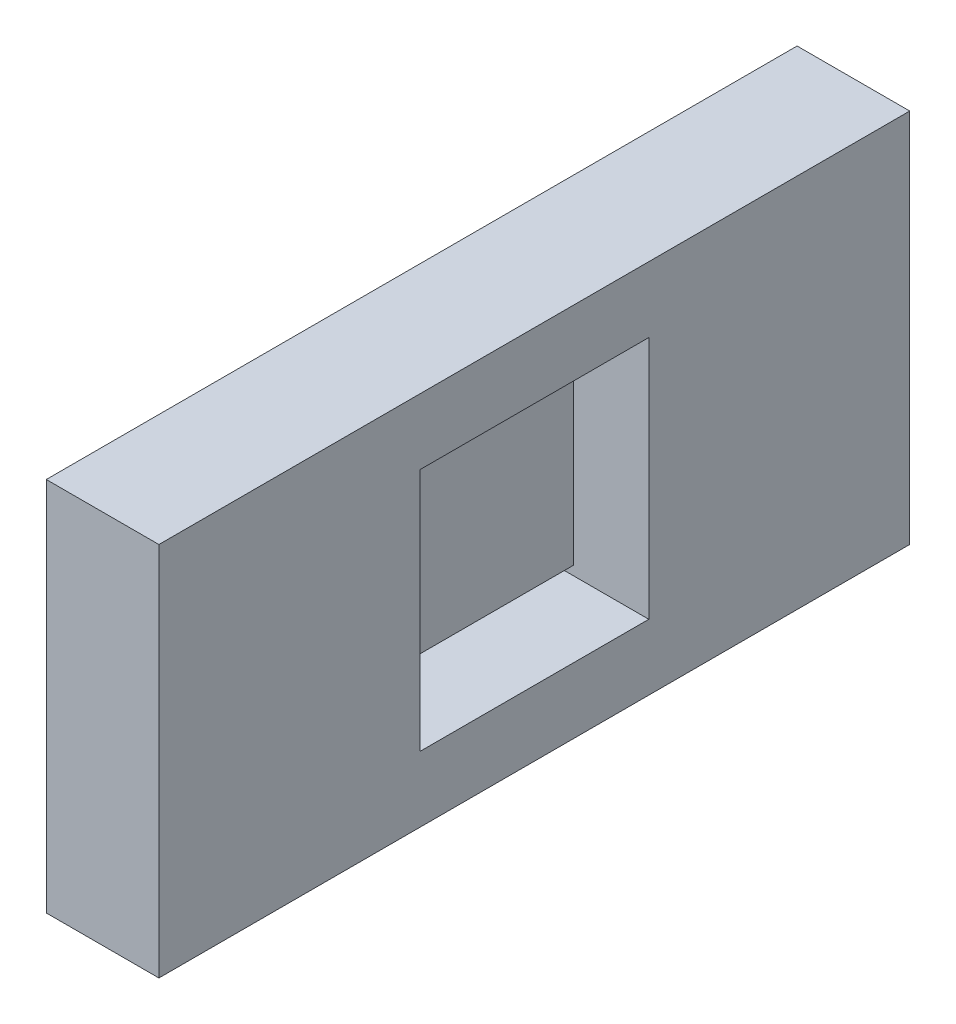
SolidWorks part; units mm, degrees
ref_plane "Front Plane" through (0, 0, 0) normal (0, 0, 1) x (1, 0, 0)
ref_plane "Top Plane" through (0, 0, 0) normal (0, 1, 0) x (1, 0, 0)
ref_plane "Right Plane" through (0, 0, 0) normal (1, 0, 0) x (0, 0, -1)
sketch "Sketch1" plane through (0, 0, 0) normal (1, 0, 0) x (0, 0, -1)
  line L1 (0, 0) -> (12.2, 0)
  line L2 (0, 0) -> (0, 13)
  line L3 (0, 13) -> (12.2, 13)
  line L4 (12.2, 0) -> (12.2, 13)
  line L5 (-13.9, 16.5) -> (26.1, 16.5)
  line L6 (-13.9, 16.5) -> (-13.9, -3.5)
  line L7 (-13.9, -3.5) -> (26.1, -3.5)
  line L8 (26.1, 16.5) -> (26.1, -3.5)
  point P11 (0.2576, 0)
  point P12 (-8.5614, 0.5138)
  dimension "D1" = 12.2
  dimension "D2" = 13
  dimension "D3" = 20
  dimension "D4" = 40
  dimension "D5" = 3.5
  dimension "D6" = 13.9
extrude "Boss-Extrude1" add sketch "Sketch1" along normal blind 2 contours L1 L4 L3 L2 region at (0, 6.5, -6.1)
extrude "Boss-Extrude4" add sketch "Sketch1<5>" along normal blind 6
sketch "Sketch1<5>" plane through (0, 0, 0) normal (1, 0, 0) x (0, 0, -1) same geometry as "Sketch1"
sketch "Sketch5" plane through (2, 0, 0) normal (1, 0, 0) x (0, 0, -1)
  line L1 (12.2, 0) -> (12.2, 13) construction
  line L2 (0, 0) -> (12.2, 0)
  line L3 (0, 0) -> (0, 0.5)
  line L4 (0, 0.5) -> (12.2, 0.5)
  line L6 (12.2, 0) -> (12.2, 0.5)
  line L8 (0, 13) -> (12.2, 13)
  line L9 (0, 13) -> (0, 12.5)
  line L10 (0, 12.5) -> (12.2, 12.5)
  line L11 (12.2, 13) -> (12.2, 12.5)
  dimension "D1" = 0.5
  dimension "D2" = 0.5
extrude "Cut-Extrude4" cut sketch "Sketch5" against normal up to surface (2 mm away) up to face at (0, 6.5, -6.1)
